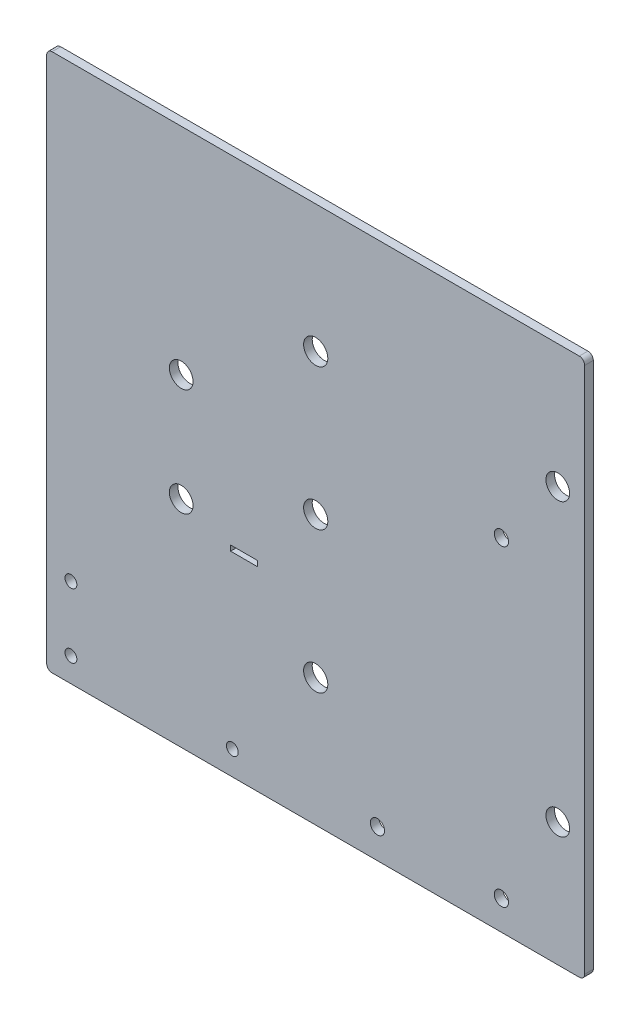
SolidWorks part; units mm, degrees
material "FR4_stuffedProtoboard"
ref_plane "Front Plane" through (0, 0, 0) normal (0, 0, 1) x (1, 0, 0)
ref_plane "Top Plane" through (0, 0, 0) normal (0, 1, 0) x (1, 0, 0)
ref_plane "Right Plane" through (0, 0, 0) normal (1, 0, 0) x (0, 0, -1)
sketch "Sketch1" plane through (0, 0, 0) normal (0, 0, 1) x (1, 0, 0)
  line L1 (-50, -50) -> (50, -50)
  line L2 (-50, -50) -> (-50, 50)
  line L3 (-50, 50) -> (50, 50)
  line L4 (50, -50) -> (50, 50)
  line L5 (-50, -50) -> (50, 50) construction
  line L6 (-50, 50) -> (50, -50) construction
  dimension "D1" = 100
extrude "Boss-Extrude1" add sketch "Sketch1" along normal blind 1.6
sketch "Sketch2" [suppressed] plane through (0, 0, 1.6) normal (0, 0, 1) x (1, 0, 0)
  circle A0 centre (0, 0) radius 50
  line M2 (50, -50) -> (50, 50)
  line M3 (50, 50) -> (-50, 50)
  line M4 (-50, 50) -> (-50, -50)
  line M5 (-50, -50) -> (50, -50)
  dimension "D1" = 100
extrude "Cut-Extrude1" [suppressed] cut sketch "Sketch2" against normal blind 1.6 contours A0 M3 M4 | A0 M4 M5 | A0 M5 M2 | A0 M2 M3
sketch "Sketch3" plane through (0, 0, 0) normal (0, 0, -1) x (-1, 0, 0)
  line L0 (-40, -22) -> (-50, -22) construction
  line L1 (-40, -32) -> (-40, -22) construction
  line L2 (-50, -32) -> (-40, -32) construction
  line L3 (-50, -22) -> (-50, -32) construction
  line L4 (-40, -22) -> (-50, -22)
  line L5 (-40, -32) -> (-40, -22)
  line L6 (-50, -32) -> (-40, -32)
  line L7 (-50, -22) -> (-50, -32)
  line L8 (-40, 22) -> (-40, 32) construction
  line L9 (-40, 32) -> (-50, 32) construction
  line L10 (-50, 32) -> (-50, 22) construction
  line L11 (-50, 22) -> (-40, 22) construction
  line L12 (-40, 22) -> (-40, 32)
  line L13 (-40, 32) -> (-50, 32)
  line L14 (-50, 32) -> (-50, 22)
  line L15 (-50, 22) -> (-40, 22)
  line L16 (5, -22) -> (-5, -22) construction
  line L17 (5, -32) -> (5, -22) construction
  line L18 (-5, -32) -> (5, -32) construction
  line L19 (-5, -22) -> (-5, -32) construction
  line L20 (5, -22) -> (-5, -22)
  line L21 (5, -32) -> (5, -22)
  line L22 (-5, -32) -> (5, -32)
  line L23 (-5, -22) -> (-5, -32)
  line L24 (5, 22) -> (5, 32) construction
  line L25 (5, 32) -> (-5, 32) construction
  line L26 (-5, 32) -> (-5, 22) construction
  line L27 (-5, 22) -> (5, 22) construction
  line L28 (5, 22) -> (5, 32)
  line L29 (5, 32) -> (-5, 32)
  line L30 (-5, 32) -> (-5, 22)
  line L31 (-5, 22) -> (5, 22)
  line L32 (17, 25) -> (45, 25) construction
  line L33 (45, 25) -> (45, -25) construction
  line L34 (17, -25) -> (45, -25) construction
  line L35 (17, 25) -> (17, -25) construction
  line L36 (17, 25) -> (45, 25)
  line L37 (45, 25) -> (45, -25)
  line L38 (17, -25) -> (45, -25)
  line L39 (17, 25) -> (17, -25)
  circle A0 centre (0, 26.25) radius 2.2479 construction
  circle A2 centre (0, 26.25) radius 2.2479
  circle A3 centre (0, 0) radius 2.2479
  circle A4 centre (-34.525, -44.525) radius 1.325 construction
  circle A6 centre (-34.525, -44.525) radius 1.325
  circle A8 centre (0, -26.25) radius 2.2479 construction
  circle A9 centre (0, -26.25) radius 2.2479
  circle A11 centre (-45, -27) radius 2.2
  circle A13 centre (-45, 27) radius 2.2
  circle A14 centre (-34.525, 13.525) radius 1.325 construction
  circle A15 centre (-34.525, 13.525) radius 1.325
  circle A16 centre (15.5, -45.5) radius 1.1 construction
  circle A17 centre (15.5, -45.5) radius 1.1
  circle A18 centre (45.5, -45.5) radius 1.1 construction
  circle A19 centre (45.5, -45.5) radius 1.1
  circle A20 centre (45.5, -33.5) radius 1.1 construction
  circle A21 centre (45.5, -33.5) radius 1.1
  circle A22 centre (-11.475, -44.525) radius 1.325 construction
  circle A23 centre (-11.475, -44.525) radius 1.325
  circle A24 centre (25, -10) radius 2.2 construction
  circle A25 centre (25, -10) radius 2.2
  circle A26 centre (25, 10) radius 2.2 construction
  circle A27 centre (25, 10) radius 2.2
  circle A28 centre (-45, 27) radius 2.2 construction
  circle A29 centre (-45, 27) radius 2.2
  circle A30 centre (-45, -27) radius 2.2 construction
  circle A31 centre (-45, -27) radius 2.2
  dimension "D1" = 4.4958
extrude "Cut-Extrude2" cut sketch "Sketch3" against normal up to surface (1.6 mm away) contours A11 | A2 | A25 | A27 | A6 | A15 | A13 | A3 | A9 | A23 | A17 | A19 | A21 region at (0, 26.25, 0) region at (45, -27, 0) region at (-25, -10, 0) region at (-25, 10, 0) up to face at (0, 0, 1.6)
sketch "Sketch4" plane through (0, 0, 1.6) normal (0, 0, 1) x (1, 0, 0)
  line L0 (38, -44.25) -> (38, -18.925) construction
  line L5 (38, -44.25) -> (38, -18.925)
  line L6 (11.75, -48) -> (34.25, -48) construction
  line L7 (11.75, -48) -> (34.25, -48)
  line L8 (8, -44.25) -> (8, 13.25) construction
  line L9 (8, -44.25) -> (8, 13.25)
  line L10 (-13.3154, -13.3154) -> (-13.3154, -28.3154) construction
  line L11 (33, -3) -> (33, -48) construction
  line L13 (34.25, 17) -> (11.75, 17)
  line L14 (38, 13.25) -> (38, -18.925)
  line L15 (-48, -48) -> (-13, -48) construction
  line L16 (-48, -48) -> (-13, -48)
  line L17 (-48, -31) -> (-48, -48) construction
  line L18 (-48, -31) -> (-48, -48)
  line L19 (-13, -40.5) -> (-13, -32.5) construction
  line L20 (-13, -40.5) -> (-13, -32.5)
  line L21 (-13, -48) -> (-13, -40.5) construction
  line L22 (-13, -48) -> (-13, -40.5)
  line L23 (-13, -32.5) -> (-13, -31) construction
  line L24 (-13, -32.5) -> (-13, -31)
  line L25 (-13, -31) -> (-48, -31) construction
  line L26 (-13, -31) -> (-48, -31)
  line L27 (-20, -34) -> (-20, -48) construction
  line L28 (-10.8154, -12.8154) -> (-15.8154, -12.8154)
  line L29 (-10.8154, -12.8154) -> (-10.8154, -13.8154)
  line L30 (-10.8154, -13.8154) -> (-15.8154, -13.8154)
  line L31 (-15.8154, -12.8154) -> (-15.8154, -13.8154)
  line L32 (-10.8154, -12.8154) -> (-15.8154, -13.8154) construction
  line L33 (-10.8154, -13.8154) -> (-15.8154, -12.8154) construction
  arc A0 (34.25, -48) -> (38, -44.25) centre (34.25, -44.25) ccw construction
  arc A1 (34.25, -48) -> (38, -44.25) centre (34.25, -44.25) ccw
  arc A2 (8, -44.25) -> (11.75, -48) centre (11.75, -44.25) ccw construction
  arc A3 (8, -44.25) -> (11.75, -48) centre (11.75, -44.25) ccw
  arc A4 (11.75, 17) -> (8, 13.25) centre (11.75, 13.25) ccw construction
  arc A5 (11.75, 17) -> (8, 13.25) centre (11.75, 13.25) ccw
  arc A6 (38, 13.25) -> (34.25, 17) centre (34.25, 13.25) ccw construction
  arc A7 (38, 13.25) -> (34.25, 17) centre (34.25, 13.25) ccw
  spline S1 degree 3 poles (-2530.9371, 5388.7614) (3519.6841, -4992.2288) (-4340.4984, 4283.8838) (4902.2932, -3391.6573) knots -64.206994 -64.206994 -64.206994 -64.206994 64.474116 64.474116 64.474116 64.474116 only from (-11.0484, -16.3728) to (-13.3154, -13.3154) construction
  spline S3 degree 3 poles (-13.0064, -13.8154) (-13.1119, -13.6503) (-13.2149, -13.4836) (-13.3154, -13.3154) knots 0.845859 0.845859 0.845859 0.845859 1 1 1 1 construction
  text T0 "Raspberry Pi Zero W" font "Century Gothic" height 2
  text T1 "Atheros" font "Century Gothic" height 2
  text T2 "ANTENNA HOLE" font "Century Gothic" height in points 5
  dimension "D5" = 1
  dimension "D1" = 5
  dimension "D2" = 20
  dimension "D3" = 3
  dimension "D4" = 7
  dimension "D6" = 15
  dimension "D7" = 5
fillet "Fillet1" radius 1 4 edges at (-50, -50, 0.8) (-50, 50, 0.8) (50, -50, 0.8) (50, 50, 0.8)
extrude "Cut-Extrude3" cut sketch "Sketch4" against normal up to surface (1.6 mm away) contours L28 L31 L30 L29 region at (-13.3154, -13.3154, 1.6) up to face at (-2.2479, -26.25, 0)
